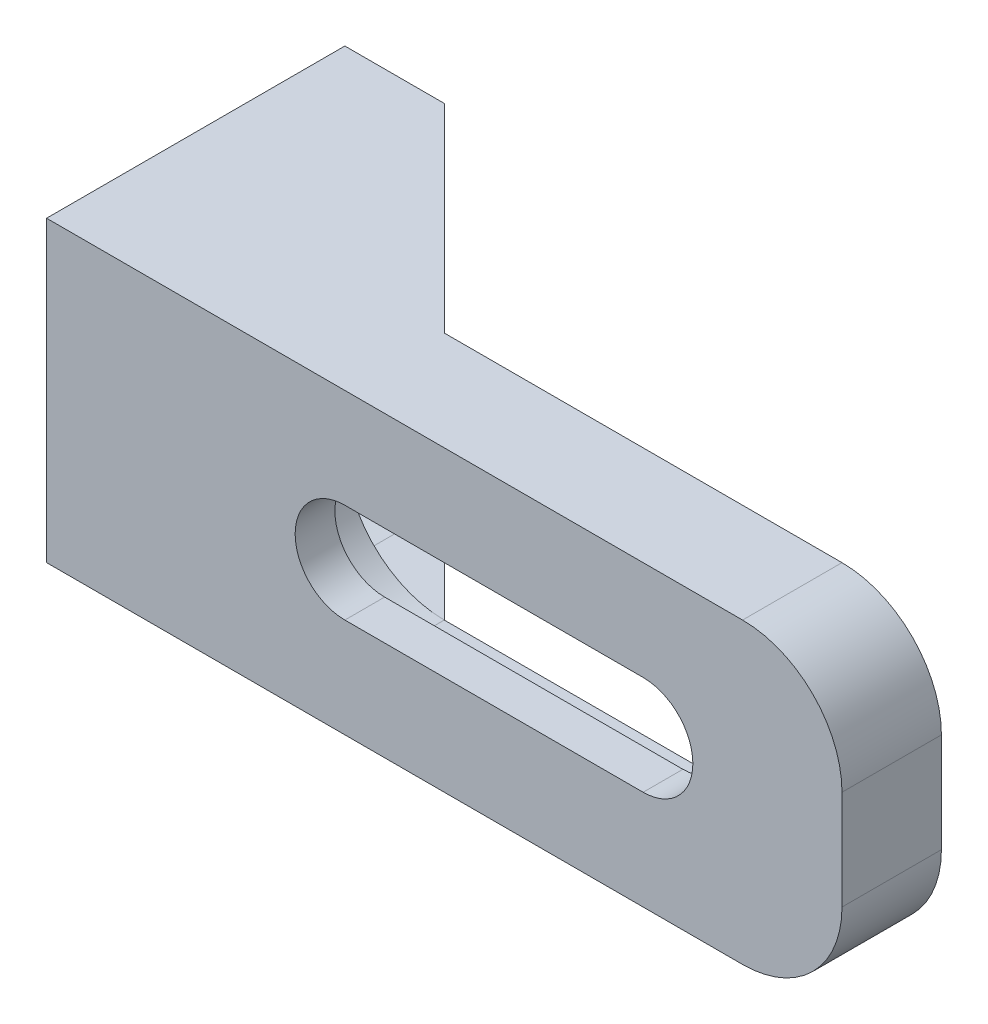
SolidWorks part; units mm, degrees
ref_plane "Спереди" through (0, 0, 0) normal (0, 0, 1) x (1, 0, 0)
ref_plane "Сверху" through (0, 0, 0) normal (0, 1, 0) x (1, 0, 0)
ref_plane "Справа" through (0, 0, 0) normal (1, 0, 0) x (0, 0, -1)
sketch "Эскиз1" plane through (0, 0, 0) normal (0, 0, 1) x (1, 0, 0)
  line L0 (-15, 7.5) -> (-15, -7.5)
  line L1 (-20, -7.5) -> (15, -7.5)
  line L2 (-20, -7.5) -> (-20, 7.5)
  line L3 (-20, 7.5) -> (15, 7.5)
  line L4 (20, -2.5) -> (20, 2.5)
  line L5 (-20, -7.5) -> (20, 7.5) construction
  line L6 (-20, 7.5) -> (20, -7.5) construction
  line L7 (0, 0) -> (14.9169, 0) construction
  line L8 (-10, 0) -> (10, 0) construction
  line L10 (-10, 5) -> (10, 5)
  line L14 (-10, -5) -> (10, -5)
  line L15 (10, 0) -> (-5, 0) construction
  line L16 (10, -5) -> (-5, -5)
  line L17 (10, 5) -> (-5, 5)
  line L18 (-5, 0) -> (10, 0) construction
  line L19 (-5, 2.5) -> (10, 2.5)
  line L20 (-5, -2.5) -> (10, -2.5)
  arc A7 (-10, 5) -> (-10, -5) centre (-10, 0) ccw
  arc A8 (10, -5) -> (10, 5) centre (10, 0) ccw
  arc A9 (10, -5) -> (10, 5) centre (10, 0) ccw
  arc A10 (-5, 5) -> (-5, -5) centre (-5, 0) ccw
  arc A11 (-5, 2.5) -> (-5, -2.5) centre (-5, 0) ccw
  arc A12 (10, -2.5) -> (10, 2.5) centre (10, 0) ccw
  arc A13 (20, 2.5) -> (15, 7.5) centre (15, 2.5) ccw
  arc A14 (15, -7.5) -> (20, -2.5) centre (15, -2.5) ccw
  point P0 (0, 0)
  point P12 (0, 0)
  point P17 (15, 0)
  point P20 (2.5, 0)
  point P25 (-10, 0)
  point P28 (2.5, 0)
  dimension "D5" = 35
  dimension "D7" = 10
  dimension "D9" = 5
  dimension "D8" = 5
  dimension "D6" = 5
  dimension "D10" = 5
  dimension "D1" = 40
  dimension "D2" = 15
  dimension "D3" = 5
  dimension "D4" = 2.5
extrude "Бобышка-Вытянуть1" add sketch "Эскиз1" against normal blind 2 contours L10 A10 L14 A8 A12 L20 A11 L19 | L3 L2 L1 L0 | L1 A14 L4 A13 L3 L0 A7 L10 A8 L14 | A10 L10 A7 L14 region at (-11.427, 0, 0) region at (0, 7.1192, 0) region at (-17.5, 0, 0) region at (2.5, 4.7307, 0)
extrude "Бобышка-Вытянуть2" add sketch "Эскиз1<3>" against normal blind 5 contours L1 A14 L4 A13 L3 L0 A7 L10 A8 L14 | L3 L2 L1 L0 | A10 L10 A7 L14 region at (-11.427, 0, 0) region at (0, 7.1192, 0) region at (-17.5, 0, 0)
sketch "Эскиз1<3>" plane through (0, 0, 0) normal (0, 0, 1) x (1, 0, 0) same geometry as "Эскиз1"
extrude "Бобышка-Вытянуть3" add sketch "Эскиз1<4>" against normal blind 15 contours L3 L2 L1 L0 region at (-17.5, 0, 0)
sketch "Эскиз1<4>" plane through (0, 0, 0) normal (0, 0, 1) x (1, 0, 0) same geometry as "Эскиз1"
sketch "Эскиз2" plane through (0, 7.5, 0) normal (0, 1, 0) x (1, 0, 0)
  line L0 (-15, 15) -> (-5, 5)
  line L1 (-15, 5) -> (15, 5) construction
  line L2 (-15, 15) -> (-15, 5)
  line L3 (-15, 5) -> (-5, 5)
  dimension "D1" = 135
extrude "Бобышка-Вытянуть4" add sketch "Эскиз2" against normal blind 15
extrude "Вырез-Вытянуть1" cut sketch "Эскиз1<5>" against normal blind 15 contours L20 A12 L19 A11 region at (2.5, 0, 0)
sketch "Эскиз1<5>" plane through (0, 0, 0) normal (0, 0, 1) x (1, 0, 0) same geometry as "Эскиз1"
extrude "Вырез-Вытянуть2" cut sketch "Эскиз1<6>" against normal blind 15 contours L10 A10 L14 A8 A12 L20 A11 L19 region at (2.5, 4.7307, 0)
sketch "Эскиз1<6>" plane through (0, 0, 0) normal (0, 0, 1) x (1, 0, 0) same geometry as "Эскиз1"
extrude "Вырез-Вытянуть3" cut sketch "Эскиз1<7>" against normal blind 15 contours A10 L10 A7 L14 region at (-11.427, 0, 0)
sketch "Эскиз1<7>" plane through (0, 0, 0) normal (0, 0, 1) x (1, 0, 0) same geometry as "Эскиз1"
extrude "Бобышка-Вытянуть9" add sketch "Эскиз1<12>" against normal blind 2 contours A10 L10 A7 L14 | L10 A10 L14 A8 A12 L20 A11 L19 region at (-11.427, 0, 0) region at (2.5, 4.7307, 0)
sketch "Эскиз1<12>" plane through (0, 0, 0) normal (0, 0, 1) x (1, 0, 0) same geometry as "Эскиз1"
extrude "Бобышка-Вытянуть10" add sketch "Эскиз1<13>" against normal blind 5 contours A10 L10 A7 L14 region at (-11.427, 0, 0)
sketch "Эскиз1<13>" plane through (0, 0, 0) normal (0, 0, 1) x (1, 0, 0) same geometry as "Эскиз1"
